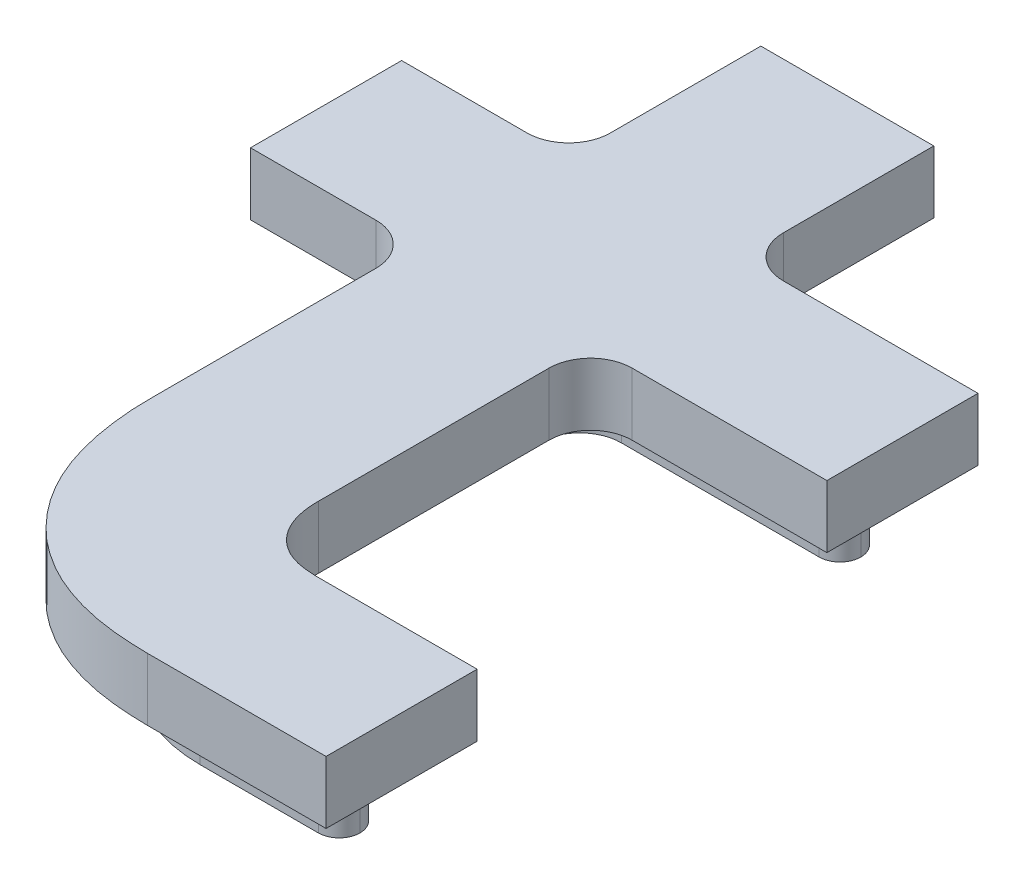
SolidWorks part; units mm, degrees
material "Красное дерево"
ref_plane "Спереди" through (0, 0, 0) normal (0, 0, 1) x (1, 0, 0)
ref_plane "Сверху" through (0, 0, 0) normal (0, 1, 0) x (1, 0, 0)
ref_plane "Справа" through (0, 0, 0) normal (1, 0, 0) x (0, 0, -1)
sketch "Эскиз t" plane through (0, 0, 0) normal (0, 1, 0) x (1, 0, 0)
  line L0 (0, 153.8462) -> (40.1397, 153.8462)
  line L1 (40.1397, 153.8462) -> (40.1397, 200)
  line L2 (40.1397, 200) -> (81.6862, 200)
  line L3 (81.6862, 200) -> (81.6862, 153.8462)
  line L4 (81.6862, 153.8462) -> (138.4571, 153.8462)
  line L5 (138.4571, 153.8462) -> (138.4571, 117.5481)
  line L6 (138.4571, 117.5481) -> (81.6862, 117.5481)
  line L7 (81.6862, 117.5481) -> (81.6862, 52.2436)
  line L8 (96.9106, 36.2981) -> (135.6926, 36.2981)
  line L9 (135.6926, 36.2981) -> (135.6926, 0)
  line L10 (135.6926, 0) -> (92.7439, 0)
  line L11 (40.1397, 53.8061) -> (40.1397, 117.5481)
  line L12 (40.1397, 117.5481) -> (0, 117.5481)
  line L13 (0, 117.5481) -> (0, 153.8462)
  line L14 (0, -40.814) -> (0, 222.1621) construction
  line L15 (-87.9774, 0) -> (197.2997, 0) construction
  spline S0 degree 3 poles (81.6862, 52.2436) (81.6553, 49.9829) (82.0854, 46.6905) (83.8177, 42.7933) (85.6039, 40.4398) (87.8479, 38.5612) (91.5433, 36.6867) (94.7583, 36.3504) (96.9106, 36.2981) knots 0 0 0 0 0.271489 0.391201 0.507819 0.622674 0.739445 1 1 1 1
  spline S1 degree 3 poles (92.7439, 0) (88.8492, 0.0503) (83.1165, 0.3658) (75.8105, 1.8985) (70.7972, 3.4788) (66.0841, 5.4542) (61.7495, 7.9819) (57.6914, 10.8559) (54.0534, 14.2541) (50.7675, 18.0064) (47.9085, 22.1198) (45.4837, 26.563) (43.5199, 31.3617) (42.0023, 36.5049) (40.5498, 43.9894) (40.0847, 49.8218) (40.1397, 53.8061) knots 0 0 0 0 0.137099 0.200908 0.261935 0.321669 0.380134 0.437984 0.496125 0.554688 0.613033 0.671859 0.732277 0.794963 0.860058 1 1 1 1
  dimension "D1" = 40.1397
  dimension "D2" = 40.1397
  dimension "D3" = 41.5465
  dimension "D4" = 41.5465
  dimension "D5" = 117.5481
  dimension "D6" = 36.2981
  dimension "D7" = 117.5481
  dimension "D8" = 36.2981
  dimension "D9" = 138.4571
  dimension "D10" = 200
  dimension "D11" = 36.2981
  dimension "D12" = 135.6926
extrude "t" add sketch "Эскиз t" along normal blind 15
sketch "Эскиз крепежа подсветки" plane through (0, 0, 0) normal (0, 1, 0) x (1, 0, 0)
  line L0 (60.9132, 190) -> (60.9132, 49.5113)
  line L1 (92.2755, 18.149) -> (125.6971, 18.149)
  line L2 (10, 135.699) -> (128.4571, 135.699)
  arc A0 (60.9132, 49.5113) -> (92.2755, 18.149) centre (92.2755, 49.5113) ccw
  dimension "D1" = 60.9132
  dimension "D2" = 18.149
  dimension "D3" = 135.699
  dimension "D4" = 190
  dimension "D5" = 10
  dimension "D6" = 128.4571
  dimension "D7" = 125.6971
extrude "Вытянуть-Тонкостенный1" add sketch "Эскиз крепежа подсветки" against normal blind 15 thin thin type mid plane wall 10
fillet "Внешнее скругление под ленту" radius 5 8 edges at (128.4571, -7.5, -140.699) (128.4571, -7.5, -130.699) (125.6971, -7.5, -23.149) (125.6971, -7.5, -13.149) (10, -7.5, -130.699) (10, -7.5, -140.699) (55.9132, -7.5, -190) (65.9132, -7.5, -190)
fillet "Внутренне скругление под ленту" radius 10 4 edges at (65.9132, -7.5, -130.699) (55.9132, -7.5, -130.699) (55.9132, -7.5, -140.699) (65.9132, -7.5, -140.699)
fillet "Скругление под фрезу" radius 10 4 edges at (40.1397, 7.5, -117.5481) (81.6862, 7.5, -117.5481) (81.6862, 7.5, -153.8462) (40.1397, 7.5, -153.8462)
sketch "Эскиз разметки под шурупы" plane through (0, 0, 0) normal (0, 1, 0) x (1, 0, 0)
  circle A0 centre (60.9132, 135.699) radius 1.5
  circle A1 centre (120.6971, 18.149) radius 1.5
  circle A2 centre (123.4571, 135.699) radius 1.5
  dimension "D1" = 3
  dimension "D2" = 3
  dimension "D7" = 3
  dimension "D5" = 18.149
  dimension "D6" = 120.6971
  dimension "D8" = 2.76
  dimension "D4" = 117.55
  dimension "D3" = 59.7838
extrude "Разметка под шурупы" cut sketch "Эскиз разметки под шурупы" against normal through all
equation "\"drill\"= 3мм"
equation "\"D1@Эскиз разметки под шурупы\" = \"drill\""
equation "\"D2@Эскиз разметки под шурупы\" = \"drill\""
equation "\"D7@Эскиз разметки под шурупы\"=\"drill\""
